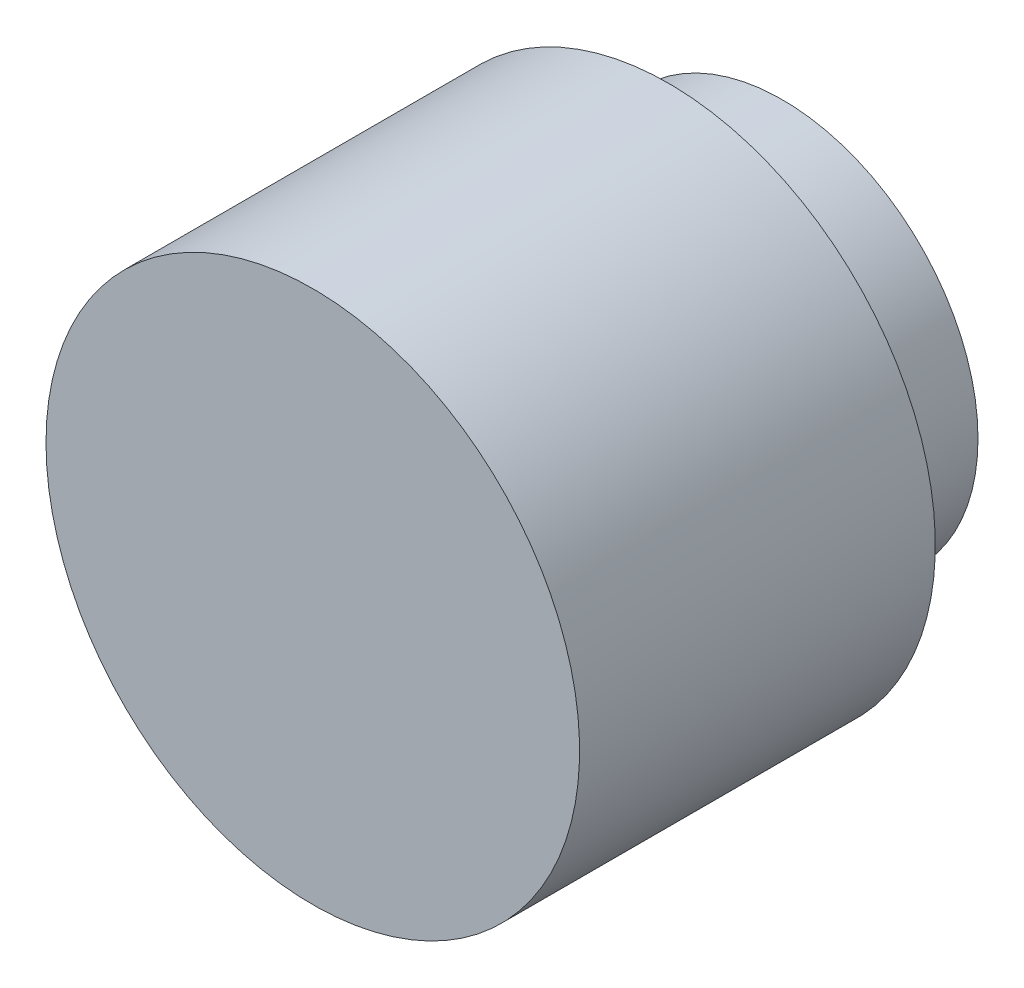
SolidWorks part; units mm, degrees
ref_plane "Plano frontal" through (0, 0, 0) normal (0, 0, 1) x (1, 0, 0)
ref_plane "Plano superior" through (0, 0, 0) normal (0, 1, 0) x (1, 0, 0)
ref_plane "Plano direito" through (0, 0, 0) normal (1, 0, 0) x (0, 0, -1)
sketch "Esboço1" plane through (0, 0, -10) normal (0, 0, 1) x (1, 0, 0)
  circle A0 centre (153.7069, -5.1317) radius 5.5 construction
  circle A1 centre (153.7069, -5.1317) radius 8.5 construction
  circle A3 centre (153.7069, -5.1317) radius 5.5
  dimension "D2" = 3
extrude "Ressalto-extrusão1" add sketch "Esboço1" against normal up to surface (3.2 mm away) contours A3
sketch "Esboço2" plane through (0, 0, -10) normal (0, 0, 1) x (1, 0, 0)
  circle A0 centre (153.7069, -5.1317) radius 7.5
  dimension "D1" = 15
extrude "Ressalto-extrusão2" add sketch "Esboço2" along normal up to surface (10 mm away)
